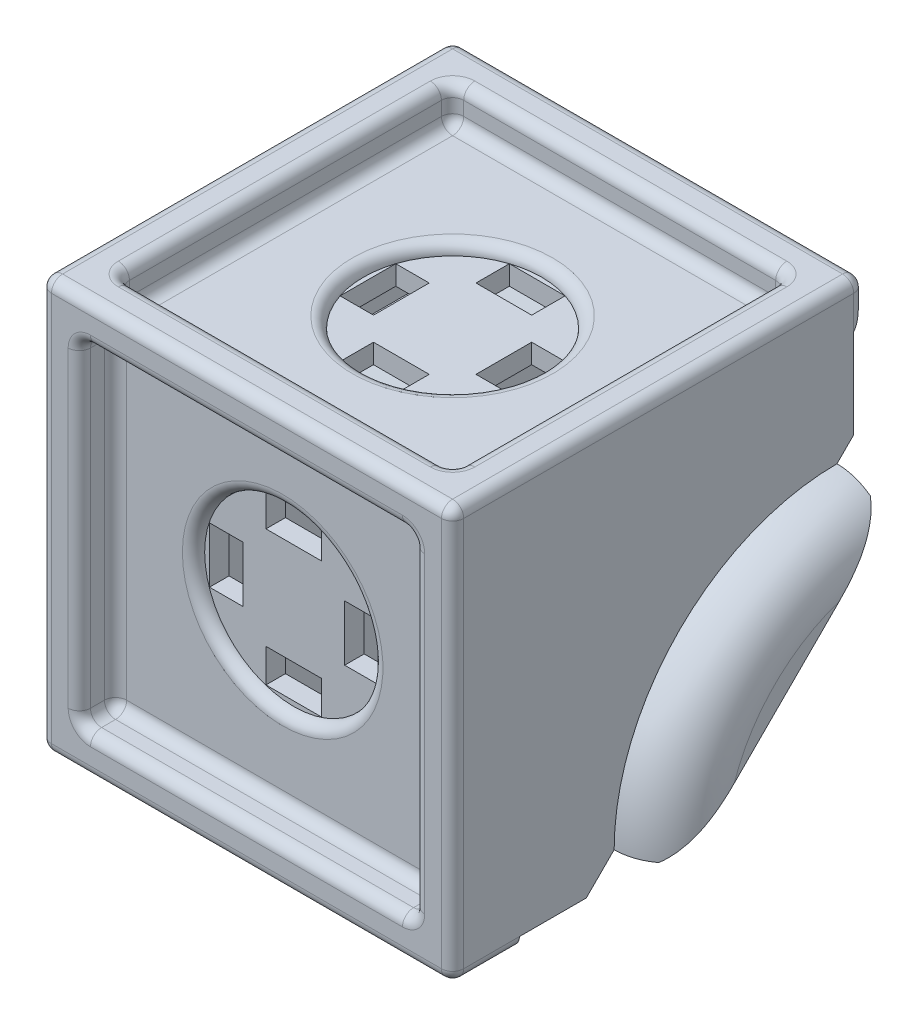
SolidWorks part; units mm, degrees
material "ABS"
ref_plane "Front Plane" through (0, 0, 0) normal (0, 0, 1) x (1, 0, 0)
ref_plane "Top Plane" through (0, 0, 0) normal (0, 1, 0) x (1, 0, 0)
ref_plane "Right Plane" through (0, 0, 0) normal (1, 0, 0) x (0, 0, -1)
sketch "Sketch1" plane through (0, 0, 0) normal (0, 0, 1) x (1, 0, 0)
  line L0 (-9.398, 9.398) -> (-9.398, -9.398)
  line L1 (-9.398, -9.398) -> (9.398, -9.398)
  line L2 (9.398, -9.398) -> (9.398, 9.398)
  line L3 (9.398, 9.398) -> (-9.398, 9.398)
extrude "Boss-Extrude1" add sketch "Sketch1" against normal blind 3.048
ref_plane "Plane1" through (0, 9.398, 0) normal (0, 1, 0) x (1, 0, 0)
sketch "Sketch3" plane through (0, 9.398, 0) normal (0, 1, 0) x (1, 0, 0)
  line L0 (-9.398, 0) -> (-9.398, 18.796)
  line L1 (-9.398, 18.796) -> (9.398, 18.796)
  line L2 (9.398, 18.796) -> (9.398, 0)
  line L3 (9.398, 0) -> (-9.398, 0)
extrude "Boss-Extrude2" add sketch "Sketch3" against normal blind 3.048
sketch "Sketch4" plane through (0, 9.398, 0) normal (0, 1, 0) x (1, 0, 0)
  line L0 (-7.62, 1.778) -> (-7.62, 17.018)
  line L1 (-7.62, 17.018) -> (7.62, 17.018)
  line L2 (7.62, 17.018) -> (7.62, 1.778)
  line L3 (7.62, 1.778) -> (-7.62, 1.778)
extrude "Cut-Extrude1" cut sketch "Sketch4" against normal blind 1.651
sketch "Sketch5" plane through (0, 0, 0) normal (0, 0, 1) x (1, 0, 0)
  line L0 (-7.62, 7.62) -> (7.62, 7.62)
  line L1 (7.62, 7.62) -> (7.62, -7.62)
  line L2 (7.62, -7.62) -> (-7.62, -7.62)
  line L3 (-7.62, -7.62) -> (-7.62, 7.62)
extrude "Cut-Extrude2" cut sketch "Sketch5" against normal blind 1.651
sketch "Sketch6" plane through (0, 7.747, 0) normal (0, 1, 0) x (1, 0, 0)
sketch "Sketch7" plane through (0, 0, 0) normal (0, 0, 1) x (1, 0, 0)
  line L24 (1.27, -3.8427) -> (-1.27, -3.8427)
  line L30 (-1.246, 11.3973) -> (1.3229, 11.3973)
  line L32 (1.27, -3.8427) -> (1.27, -2.3187)
  line L33 (1.27, -2.3187) -> (-1.27, -2.3187)
  line L34 (-1.27, -2.3187) -> (-1.27, -3.8427)
  line L35 (-2.3187, 1.27) -> (-3.8427, 1.27)
  line L36 (-3.8427, -1.27) -> (-3.8427, 1.27)
  line L37 (-3.8427, -1.27) -> (-2.3187, -1.27)
  line L38 (-2.3187, -1.27) -> (-2.3187, 1.27)
  line L39 (1.27, 2.3187) -> (1.27, 3.8427)
  line L40 (-1.27, 3.8427) -> (1.27, 3.8427)
  line L41 (-1.27, 3.8427) -> (-1.27, 2.3187)
  line L42 (-1.27, 2.3187) -> (1.27, 2.3187)
  line L43 (2.3187, -1.27) -> (3.8427, -1.27)
  line L44 (3.8427, 1.27) -> (3.8427, -1.27)
  line L45 (3.8427, 1.27) -> (2.3187, 1.27)
  line L46 (2.3187, 1.27) -> (2.3187, -1.27)
  circle A1 centre (0, 0) radius 4.0471
  point P22 (0, 0)
  point P25 (0, 0)
  dimension "D1" = 1.524
  dimension "D2" = 2.54
  dimension "D3" = 1.27
  dimension "D4" = 4
ref_plane "Plane2" through (9.398, 0, 0) normal (1, 0, 0) x (0, 0, -1)
sketch "Sketch8" plane through (9.398, 0, 0) normal (1, 0, 0) x (0, 0, -1)
  line L0 (3.048, 6.35) -> (3.048, -8.89)
  line L1 (3.048, -9.398) -> (3.048, 6.35) construction
  line L2 (3.048, -8.89) -> (6.096, -8.89)
  line L3 (3.048, 6.35) -> (18.288, 6.35)
  line L4 (3.048, 6.35) -> (18.796, 6.35) construction
  line L5 (18.288, 6.35) -> (18.288, 3.302)
  line L6 (6.096, -8.89) -> (7.366, -7.62)
  line L7 (7.366, -7.62) -> (7.874, -7.62)
  line L8 (7.874, -7.62) -> (17.526, 2.032)
  line L9 (17.526, 2.54) -> (17.526, 2.032)
  line L10 (17.526, 2.54) -> (18.288, 3.302)
  dimension "D1" = 15.24
  dimension "D2" = 15.24
  dimension "D3" = 3.048
  dimension "D4" = 3.048
  dimension "D5" = 1.27
  dimension "D6" = 1.27
extrude "Boss-Extrude3" add sketch "Sketch8" against normal blind 1.651
fillet "Fillet1" radius 0.508 4 edges at (-7.62, 8.5725, -1.778) (7.62, 8.5725, -1.778) (7.62, 8.5725, -17.018) (-7.62, 8.5725, -17.018)
fillet "Fillet2" radius 0.508 4 edges at (-7.62, 7.62, -0.8255) (7.62, -7.62, -0.8255) (-7.62, -7.62, -0.8255) (7.62, 7.62, -0.8255)
mirror "Mirror1" about plane through (0, 0, 0) normal (1, 0, 0) of "Boss-Extrude3"
extrude "Cut-Extrude5" cut sketch "Sketch7" against normal blind 5.08 contours L41 L42 L39 L40 | L45 L46 L43 L44 | L33 L34 L24 L32 | L37 L38 L35 L36 region at (0, -3.0807, 0) region at (3.0807, 0, 0) region at (-3.0807, 0, 0) region at (0, 3.0807, 0)
sketch "Sketch11" plane through (0, 9.398, 0) normal (0, 1, 0) x (1, 0, 0)
  line L0 (0, 18.796) -> (0, 0) construction
  line L1 (9.398, 18.796) -> (-9.398, 18.796) construction
  line L10 (-4.9408, 9.398) -> (5.0621, 9.398) construction
  line L11 (-1.27, 13.2585) -> (1.27, 13.2585)
  line L12 (1.27, 13.2585) -> (1.27, 11.7345)
  line L13 (1.27, 11.7345) -> (-1.27, 11.7345)
  line L14 (-1.27, 11.7345) -> (-1.27, 13.2585)
  line L15 (3.8605, 10.668) -> (3.8605, 8.128)
  line L16 (3.8605, 8.128) -> (2.3365, 8.128)
  line L17 (2.3365, 8.128) -> (2.3365, 10.668)
  line L18 (2.3365, 10.668) -> (3.8605, 10.668)
  line L19 (1.27, 5.5375) -> (-1.27, 5.5375)
  line L20 (-1.27, 5.5375) -> (-1.27, 7.0615)
  line L21 (-1.27, 7.0615) -> (1.27, 7.0615)
  line L22 (1.27, 7.0615) -> (1.27, 5.5375)
  line L23 (-3.8605, 8.128) -> (-2.3365, 8.128)
  line L24 (-2.3365, 8.128) -> (-2.3365, 10.668)
  line L25 (-2.3365, 10.668) -> (-3.8605, 10.668)
  line L26 (-3.8605, 10.668) -> (-3.8605, 8.128)
  circle A0 centre (0, 9.398) radius 4.064
  dimension "D1" = 1.524
  dimension "D4" = 8.128
  dimension "D2" = 2.54
  dimension "D3" = 1.524
  dimension "D5" = 2.54
  dimension "D6" = 1.524
  dimension "D7" = 1.524
extrude "Cut-Extrude6" cut sketch "Sketch11" against normal blind 5.08 contours L14 L13 L12 L11 | L18 L17 L16 L15 | L22 L21 L20 L19 | L25 L26 L23 L24 region at (0, 9.398, -12.4965) region at (-3.0985, 9.398, -9.398) region at (3.0985, 9.398, -9.398) region at (0, 9.398, -6.2995)
sketch "Sketch12" plane through (0, 7.747, 0) normal (0, 1, 0) x (1, 0, 0)
  line L0 (-7.62, 9.398) -> (7.62, 9.398) construction
  line L1 (-7.62, 16.51) -> (-7.62, 2.286) construction
  line L2 (7.62, 2.286) -> (7.62, 16.51) construction
  circle A0 centre (0, 9.398) radius 4.064
extrude "Cut-Extrude7" cut sketch "Sketch12" against normal blind 0.508
fillet "Fillet3" radius 0.508 1 edges at (0, 7.747, -5.334)
fillet "Fillet4" radius 0.508 32 edges at (-7.4712, 7.4712, -1.651) (0, 7.62, -1.651) (7.4712, 7.4712, -1.651) (7.62, 0, -1.651) (7.4712, -7.4712, -1.651) (0, -7.62, -1.651) (-7.4712, -7.4712, -1.651) (7.4712, 7.4712, 0) (7.62, 0, 0) (7.4712, -7.4712, 0) (0, -7.62, 0) (-7.4712, -7.4712, 0) (-7.62, 0, 0) (-7.4712, 7.4712, 0) (7.4712, 7.747, -16.8692) (7.62, 7.747, -9.398) (7.4712, 7.747, -1.9268) (0, 7.747, -1.778) (-7.4712, 7.747, -1.9268) (-7.62, 7.747, -9.398) (-7.4712, 7.747, -16.8692) (7.4712, 9.398, -16.8692) (7.62, 9.398, -9.398) (7.4712, 9.398, -1.9268) (0, 9.398, -1.778) (-7.4712, 9.398, -1.9268) (-7.62, 9.398, -9.398) (-7.4712, 9.398, -16.8692) (-7.62, 0, -1.651) (0, 7.62, 0) (0, 7.747, -17.018) (0, 9.398, -17.018)
sketch "Sketch13" plane through (0, 0, 0) normal (0, 0, 1) x (1, 0, 0)
  circle A0 centre (0, 0) radius 4.064
extrude "Cut-Extrude8" cut sketch "Sketch13" against normal blind 2.159
fillet "Fillet5" radius 0.508 1 edges at (-4.064, 0, -1.651)
fillet "Fillet6" radius 0.508 11 edges at (-9.398, -9.398, -1.524) (-9.398, 7.874, -18.796) (0, 9.398, -18.796) (-9.398, 9.398, -9.398) (-9.398, 0, 0) (9.398, 7.874, -18.796) (9.398, -9.398, -1.524) (0, -9.398, 0) (9.398, 0, 0) (9.398, 9.398, -9.398) (0, 9.398, 0)
sketch "Sketch14" plane through (0, 0, -3.048) normal (0, 0, -1) x (-1, 0, 0)
  line L0 (0, 5.7276) -> (0, -6.1) construction
  line L2 (-7.747, 0.9625) -> (-2.1786, 1.8134)
  line L3 (-7.747, 6.35) -> (-7.747, -8.89) construction
  line L4 (7.747, 0.9625) -> (2.1786, 1.8134)
  line L5 (-2.1786, 1.8134) -> (-2.1786, -6.1)
  line L6 (2.1786, 1.8134) -> (2.1786, -6.1)
  line L7 (-2.1786, -6.1) -> (-7.747, -6.1)
  line L8 (2.1786, -6.1) -> (7.747, -6.1)
  line L9 (-7.747, -6.1) -> (-7.747, -7.1211)
  line L10 (7.747, -6.1) -> (7.747, -7.1211)
  line L11 (-7.747, -7.1211) -> (-1.583, -7.1211)
  line L12 (7.747, -7.1211) -> (1.583, -7.1211)
  line L13 (-1.583, -6.1) -> (-1.583, 2.8345)
  line L14 (1.583, -6.1) -> (1.583, 2.8345)
  line L15 (-1.583, 2.8345) -> (-7.747, 1.8926)
  line L16 (1.583, 2.8345) -> (7.747, 1.8926)
  line L17 (-7.747, 1.8926) -> (-7.747, 0.9625)
  line L18 (7.747, 1.8926) -> (7.747, 0.9625)
  line L19 (-1.583, -6.1) -> (1.583, -6.1)
  line L20 (-1.583, -7.1211) -> (1.583, -7.1211)
extrude "Boss-Extrude4" add sketch "Sketch14" along normal blind 15.24
sketch "Sketch15" plane through (2.1786, 0, 0) normal (1, 0, 0) x (0, 0, -1)
  line L0 (9.0298, -13.2627) -> (9.0298, 1.135)
  line L1 (9.0298, 1.135) -> (23.0041, 1.135)
  line L2 (23.0041, 1.135) -> (23.0041, 0.2528)
  line L3 (9.9826, -13.2627) -> (9.0298, -13.2627)
  arc A0 (23.0041, 0.2528) -> (9.9826, -13.2627) centre (23.0041, -12.7777) ccw
extrude "Boss-Extrude5" add sketch "Sketch15" against normal blind 4.3561
sketch "Sketch16" plane through (2.1786, 0, 0) normal (1, 0, 0) x (0, 0, -1)
  line L0 (23.0041, 0.2528) -> (23.0041, -12.7777)
  line L1 (23.0041, -12.7777) -> (9.9735, -12.7777)
  arc A0 (11.2654, -7.1211) -> (9.9826, -13.2627) centre (23.0041, -12.7777) ccw construction
  arc A1 (9.9735, -12.7777) -> (23.0041, 0.2528) centre (23.0041, -12.7777) cw
extrude "Cut-Extrude11" cut sketch "Sketch16" against normal mid plane 25.4
sketch "Sketch17" plane through (9.398, 0, 0) normal (1, 0, 0) x (0, 0, -1)
  line L0 (7.874, -7.62) -> (7.366, -7.62)
  line L1 (17.526, 2.54) -> (17.526, 2.032)
  line L2 (17.526, 2.032) -> (17.526, 2.54) construction
  line L3 (17.526, 2.032) -> (7.874, -7.62)
  arc A0 (7.366, -7.62) -> (17.526, 2.54) centre (17.526, -7.62) cw
extrude "Boss-Extrude6" add sketch "Sketch17" along normal blind 2.54
fillet "Fillet9" radius 2.54 1 edges at (11.938, -0.4358, -10.3418)
fillet "Fillet10" radius 2.54 1 edges at (0, 6.35, -18.796)
mirror "Mirror2" about plane through (0, 0, 0) normal (1, 0, 0) of "Boss-Extrude3"
sketch "Sketch19" plane through (-9.398, 0, 0) normal (-1, 0, 0) x (0, 0, 1)
  line L0 (-17.526, 2.032) -> (-17.526, 2.54)
  line L1 (-7.366, -7.62) -> (-7.874, -7.62)
  line L2 (-7.874, -7.62) -> (-17.526, 2.032)
  arc A0 (-17.526, 2.54) -> (-7.366, -7.62) centre (-17.526, -7.62) cw
extrude "Boss-Extrude7" add sketch "Sketch19" along normal blind 2.54
fillet "Fillet11" radius 2.54 1 edges at (-11.938, -0.4358, -10.3418)
